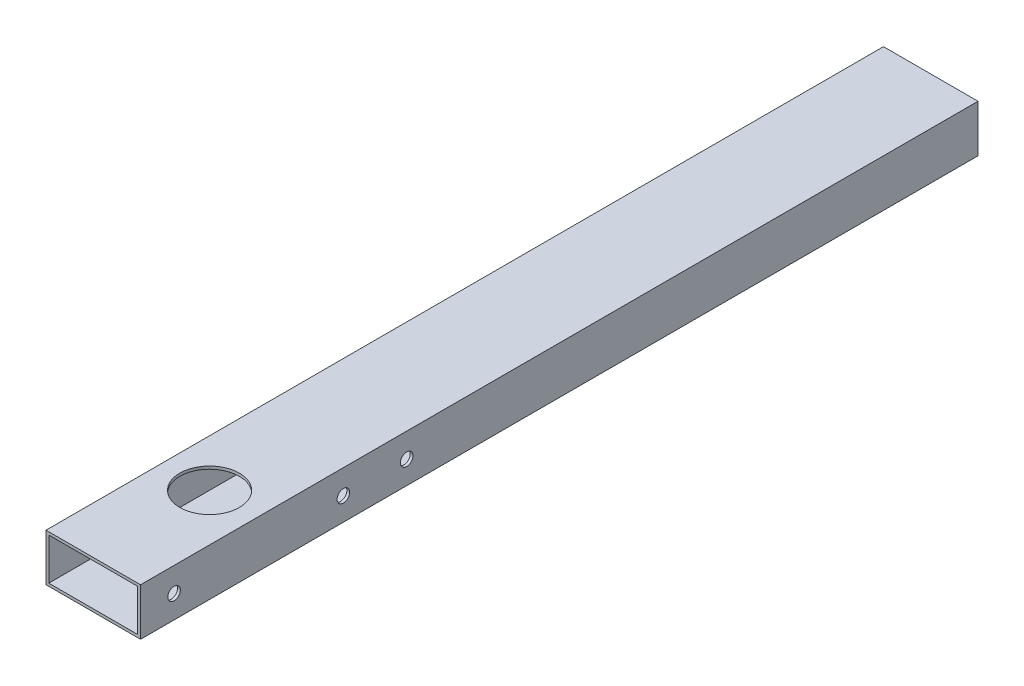
SolidWorks part; units mm, degrees
material "AISI 1015 Acero estirado en frío (SS)"
ref_plane "Alzado" through (0, 0, 0) normal (0, 0, 1) x (1, 0, 0)
ref_plane "Planta" through (0, 0, 0) normal (0, 1, 0) x (1, 0, 0)
ref_plane "Vista lateral" through (0, 0, 0) normal (1, 0, 0) x (0, 0, -1)
sketch "Croquis1" plane through (0, 0, 0) normal (0, 0, 1) x (1, 0, 0)
  line L0 (-23.9, 11.2) -> (23.9, 11.2)
  line L1 (-25.4, -12.7) -> (25.4, -12.7)
  line L2 (-25.4, -12.7) -> (-25.4, 12.7)
  line L3 (-25.4, 12.7) -> (25.4, 12.7)
  line L4 (25.4, -12.7) -> (25.4, 12.7)
  line L5 (-25.4, -12.7) -> (25.4, 12.7) construction
  line L6 (-25.4, 12.7) -> (25.4, -12.7) construction
  line L7 (23.9, -11.2) -> (23.9, 11.2)
  line L8 (-23.9, -11.2) -> (23.9, -11.2)
  line L9 (-23.9, -11.2) -> (-23.9, 11.2)
  point P0 (0, 0)
  dimension "D1" = 25.4
  dimension "D2" = 50.8
  dimension "D3" = 1.5
extrude "Saliente-Extruir1" add sketch "Croquis1" along normal blind 450
ref_plane "Plano1" through (0, 12.7, 0) normal (0, 1, 0) x (1, 0, 0)
sketch "Croquis2" plane through (0, 12.7, 0) normal (0, 1, 0) x (1, 0, 0)
  line L0 (0, -450) -> (0, -262.1851) construction
  line L1 (25.4, -450) -> (-25.4, -450) construction
  line L2 (25.4, -387.5) -> (-25.7584, -387.5) construction
  line L3 (25.4, -450) -> (25.4, 0) construction
  circle A0 centre (0, -387.5) radius 16
  dimension "D2" = 32
  dimension "D1" = 62.5
extrude "Cortar-Extruir1" cut sketch "Croquis2" against normal blind 26
hole_wizard "Taladro de margen para 1/42" positions "Croquis5" profile "Croquis6" hole size "1/4" standard "Ansi Inch" end condition through all
sketch "Croquis5" plane through (-26.4, 572.4886, 162.9891) normal (-1, 0, 0) x (0, -1, 0)
  point P0 (572.8886, 269.0109)
  point P1 (572.8886, 178.0109)
  point P2 (572.8886, 144.0109)
sketch "Croquis6" plane through (-26.4, -0.4, 432) normal (0, 1, 0) x (0, 0, 1)
  line L0 (0, 0) -> (0, 51.8)
  line L1 (0, 51.8) -> (3.3782, 51.8)
  line L2 (3.3782, 51.8) -> (3.3782, 0)
  line L3 (3.3782, 0) -> (0, 0)
  line L4 (0, -6.35) -> (0, 107.95) construction
  dimension "Diámetro de taladro hasta el siguiente" = 6.7564
  dimension "Profundidad de taladro hasta el siguiente" = 51.8
